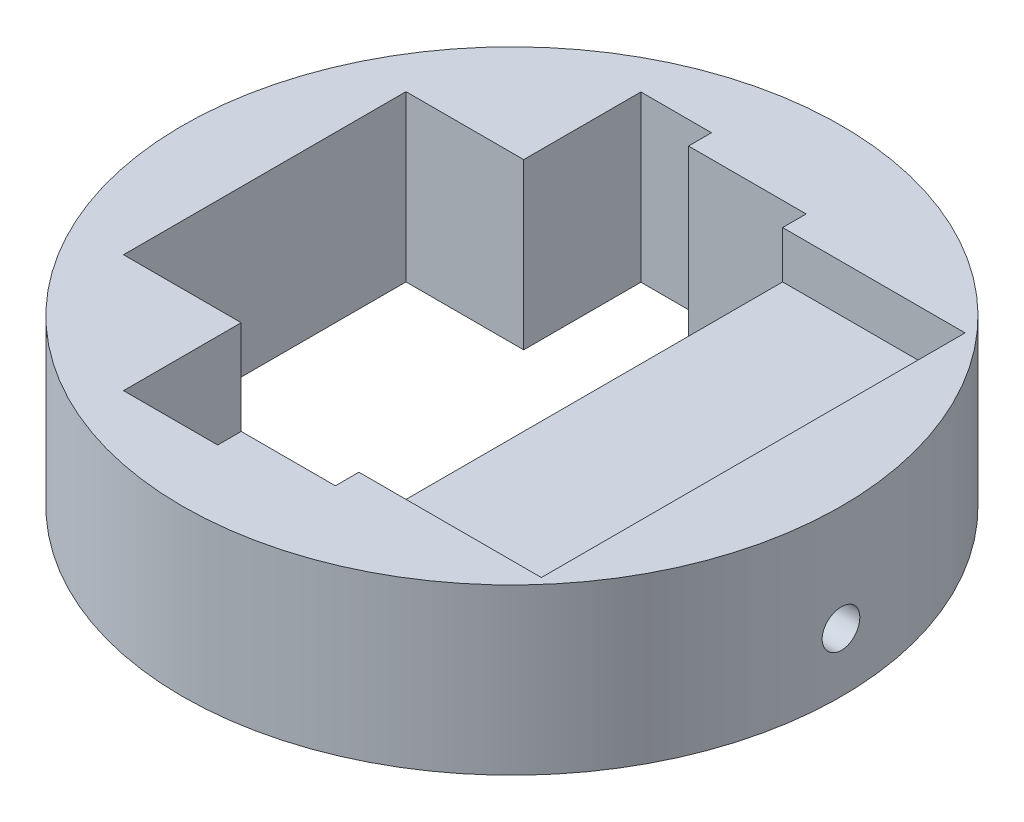
SolidWorks part; units mm, degrees
ref_plane "Спереди" through (0, 0, 0) normal (0, 0, 1) x (1, 0, 0)
ref_plane "Сверху" through (0, 0, 0) normal (0, 1, 0) x (1, 0, 0)
ref_plane "Справа" through (0, 0, 0) normal (1, 0, 0) x (0, 0, -1)
sketch "Эскиз3" plane through (0, 0, 0) normal (0, 1, 0) x (1, 0, 0)
  circle A0 centre (0, 0) radius 14
  dimension "D1" = 28
extrude "Бобышка-Вытянуть2" add sketch "Эскиз3" along normal blind 7
sketch "Эскиз8" plane through (0, 7, 0) normal (0, 1, 0) x (1, 0, 0)
  line L0 (0, 21.5769) -> (0, -20.9711) construction
  line L11 (-23.6577, 0) -> (29.9171, 0) construction
  line L24 (-2.5, 10.9773) -> (-2.5, 10)
  line L30 (-5.5, 10.9773) -> (-2.5, 10.9773)
  line L32 (-5.5, -11) -> (-1.5, -11)
  line L34 (-5.5, 6) -> (-10.5, 6)
  line L36 (-5.5, -6) -> (-10.5, -6)
  line L37 (-10.5, 6) -> (-10.5, -6)
  line L40 (-5.5, 10.9773) -> (-5.5, 6)
  line L42 (-5.5, -11) -> (-5.5, -6)
  line L43 (2.5, -10) -> (-1.5, -10)
  line L44 (2.5, -10) -> (2.5, 10)
  line L45 (2.5, 10) -> (-2.5, 10)
  line L47 (-1.5, -11) -> (-1.5, -10)
  point P0 (2.5, 0)
  point P5 (-10.5, 0)
  point P6 (0, 0)
  point P27 (0, 0)
  dimension "D4" = 3
  dimension "D1" = 20
  dimension "D2" = 5
  dimension "D3" = 12
  dimension "D5" = 5
  dimension "D7" = 4
  dimension "D8" = 22
extrude "Вырез-Вытянуть1" cut sketch "Эскиз8" against normal through all
sketch "Эскиз10" plane through (0, 7, 0) normal (0, 1, 0) x (1, 0, 0)
  line L0 (-1.75, 9) -> (-1.75, -9)
  line L5 (-50, 0) -> (50, 0) construction
  line L10 (-1.75, -9) -> (10.25, -9)
  line L12 (-1.75, 9) -> (10.25, 9)
  line L13 (10.25, -9) -> (10.25, 9)
  line L14 (-1.75, -9) -> (10.25, 9) construction
  line L15 (-1.75, 9) -> (10.25, -9) construction
  line L16 (-5.5, 10.9773) -> (-5.5, 6) construction
  line L17 (0, 17.5026) -> (0, -19.154) construction
  line L18 (-18.4407, 0) -> (24.2934, 0) construction
  point P0 (4.25, 0)
  point P5 (-5.5, 6.9527)
  dimension "D1" = 18
  dimension "D2" = 12
extrude "Вырез-Вытянуть2" cut sketch "Эскиз10" against normal blind 2
ref_plane "Плоскость1" through (14, 0, 0) normal (1, 0, 0) x (0, 0, -1)
sketch "Эскиз12" plane through (14, 0, 0) normal (1, 0, 0) x (0, 0, -1)
  circle A0 centre (0, 2.5) radius 0.8
  dimension "D2" = 1.6
  dimension "D1" = 2.5
extrude "Вырез-Вытянуть3" cut sketch "Эскиз12" against normal up to surface (11.5 mm away) up to face at (2.5, 4.75, 0)
